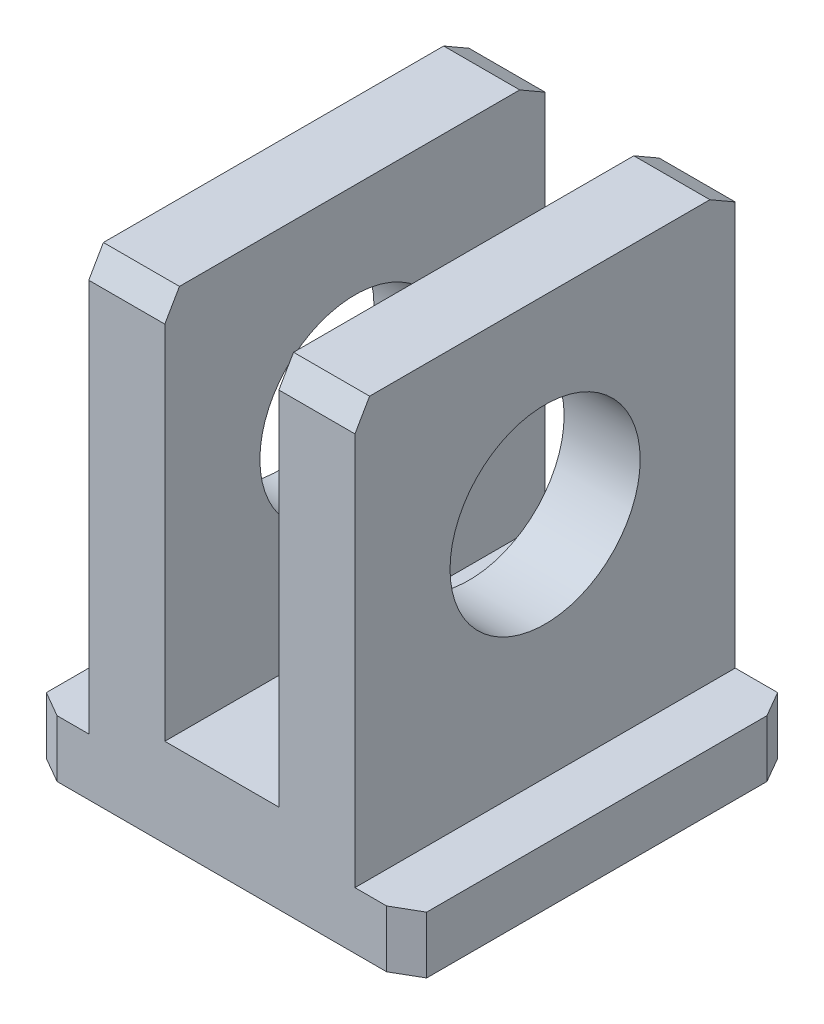
SolidWorks part; units mm, degrees
note: The reader was unsure of these and kept them because the rebuilt part matched: shared geometry of "Sketch1<3>", "Sketch1<4>".
ref_plane "Front Plane" through (0, 0, 0) normal (0, 0, 1) x (1, 0, 0)
ref_plane "Top Plane" through (0, 0, 0) normal (0, 1, 0) x (1, 0, 0)
ref_plane "Right Plane" through (0, 0, 0) normal (1, 0, 0) x (0, 0, -1)
sketch "Sketch1" plane through (0, 0, 0) normal (0, 1, 0) x (1, 0, 0)
  line L0 (4.5, 0) -> (4.5, 30)
  line L1 (0, 0) -> (15, 0)
  line L2 (0, 0) -> (0, 30)
  line L3 (0, 30) -> (15, 30)
  line L4 (15, 0) -> (15, 30)
  line L5 (10.5, 0) -> (10.5, 30)
  dimension "D1" = 15
  dimension "D2" = 4.5
  dimension "D3" = 10.5
  dimension "D4" = 30
extrude "Boss-Extrude1" add sketch "Sketch1" along normal blind 4.5 contours L5 L1 L4 L3
extrude "Boss-Extrude2" add sketch "Sketch1<3>" along normal blind 37.5 contours L1 L5 L3 L0
sketch "Sketch1<3>" plane through (0, 0, 0) normal (0, 1, 0) x (1, 0, 0) same geometry as "Sketch1"
extrude "Boss-Extrude3" add sketch "Sketch1<4>" along normal blind 7 contours L3 L2 L1 L0
sketch "Sketch1<4>" plane through (0, 0, 0) normal (0, 1, 0) x (1, 0, 0) same geometry as "Sketch1"
sketch "Sketch2" plane through (10.5, 0, 0) normal (1, 0, 0) x (0, 0, -1)
  line L0 (0, 0) -> (30, 0) construction
  line L1 (15, 37.5) -> (15, 0) construction
  line L2 (0, 37.5) -> (30, 37.5) construction
  circle A0 centre (15, 22.5) radius 7.5
  point P8 (0, 0)
  dimension "D1" = 15
  dimension "D2" = 22.5
extrude "Cut-Extrude1" cut sketch "Sketch2" against normal up to next
chamfer "Chamfer1" distance 2 angle 30 4 edges at (15, 2.25, -30) (15, 2.25, 0) (7.5, 37.5, -30) (7.5, 37.5, 0)
mirror "Mirror1" about plane through (0, 7, 0) normal (-1, 0, 0) of bodies 104
